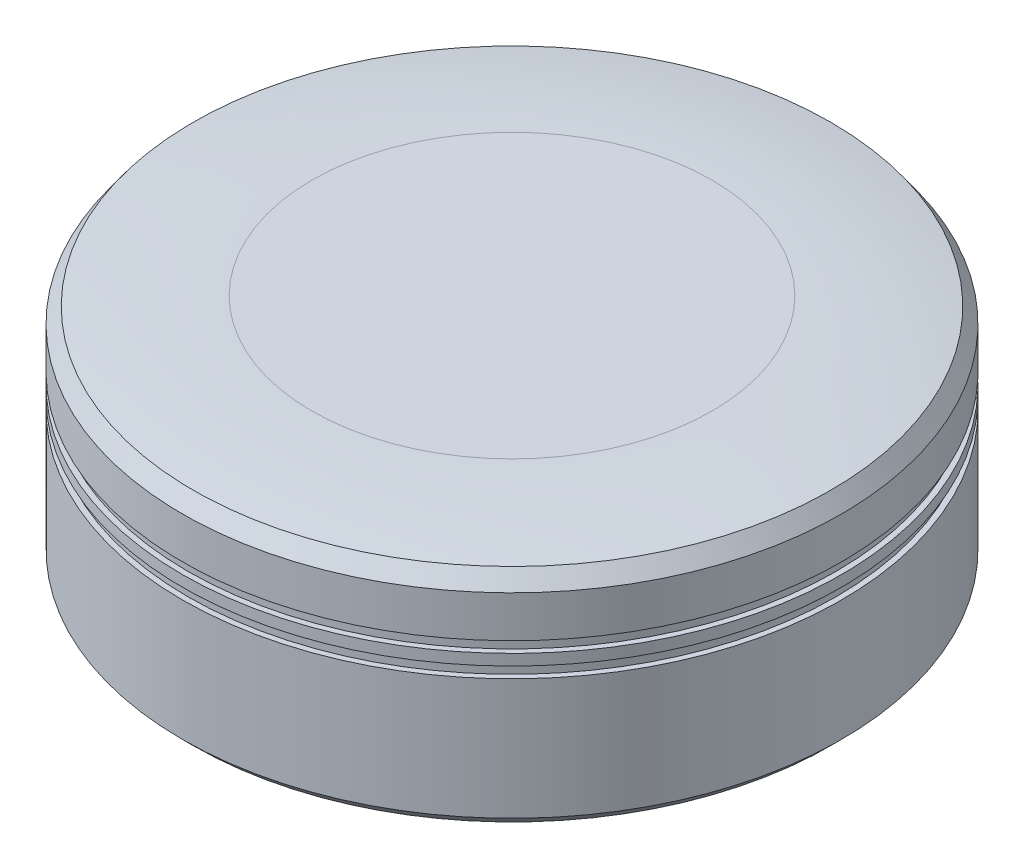
SolidWorks part; units mm, degrees
ref_plane "Front Plane" through (0, 0, 0) normal (0, 0, 1) x (1, 0, 0)
ref_plane "Top Plane" through (0, 0, 0) normal (0, 1, 0) x (1, 0, 0)
ref_plane "Right Plane" through (0, 0, 0) normal (1, 0, 0) x (0, 0, -1)
sketch "Sketch1" plane through (0, 0, 0) normal (0, 1, 0) x (1, 0, 0)
  circle A0 centre (0, 0) radius 15
  dimension "D1" = 30
extrude "Boss-Extrude1" add sketch "Sketch1" along normal blind 12
sketch "Sketch2" plane through (0, 0, 0) normal (0, -1, 0) x (1, 0, 0)
  circle A0 centre (0, 0) radius 2.95
  dimension "D1" = 5.9
extrude "Cut-Extrude1" cut sketch "Sketch2" against normal blind 9.8
sketch "Sketch3" plane through (0, 0, 0) normal (0, 0, 1) x (1, 0, 0)
  line L0 (14.75, 9) -> (15.3282, 9)
  line L1 (15.3282, 9) -> (15.3282, 8.5)
  line L2 (15.3282, 8.5) -> (14.75, 8.5)
  line L3 (14.75, 8.5) -> (14.75, 9)
  line L4 (14.75, 8) -> (15.3282, 8)
  line L5 (15.3282, 8) -> (15.3282, 7.5)
  line L6 (15.3282, 7.5) -> (14.75, 7.5)
  line L7 (14.75, 7.5) -> (14.75, 8)
  line L8 (15, 12) -> (-15, 12) construction
  line L9 (15, 12) -> (15, 7.2203) construction
  line L10 (15, 0) -> (15, 12) construction
  dimension "D1" = 0.5
  dimension "D2" = 0.5
  dimension "D3" = 0.5
  dimension "D4" = 3
  dimension "D5" = 0.25
  dimension "D6" = 0.25
sketch "Sketch4" plane through (0, 0, 0) normal (1, 0, 0) x (0, 0, -1)
  line L0 (0, 13.0008) -> (0, -3.3646) construction
revolve "Cut-Revolve1" cut sketch "Sketch3" angle 360 about L0
chamfer "Chamfer1" distance 0.5 angle 45 1 edges at (0, 12, 15)
fillet "Fillet1" radius 35 1 edges at (0, 12, 14.5)
chamfer "Chamfer3" distance 0.5 angle 45 1 edges at (0, 11.5, 15)
sketch "Sketch5" plane through (0, 0, 0) normal (0, 0, 1) x (1, 0, 0)
  line L0 (15, 0) -> (15, 7.5) construction
  line L1 (-15, 0) -> (15, 0)
  line L2 (-15, 0) -> (-15, 1.5)
  line L3 (-15, 1.5) -> (15, 1.5)
  line L4 (15, 0) -> (15, 1.5)
  dimension "D1" = 1.5
extrude "Cut-Extrude2" cut sketch "Sketch5" against normal through all and the other way through all
chamfer "Chamfer4" distance 0.5 angle 45 1 edges at (0, 1.5, 15)
